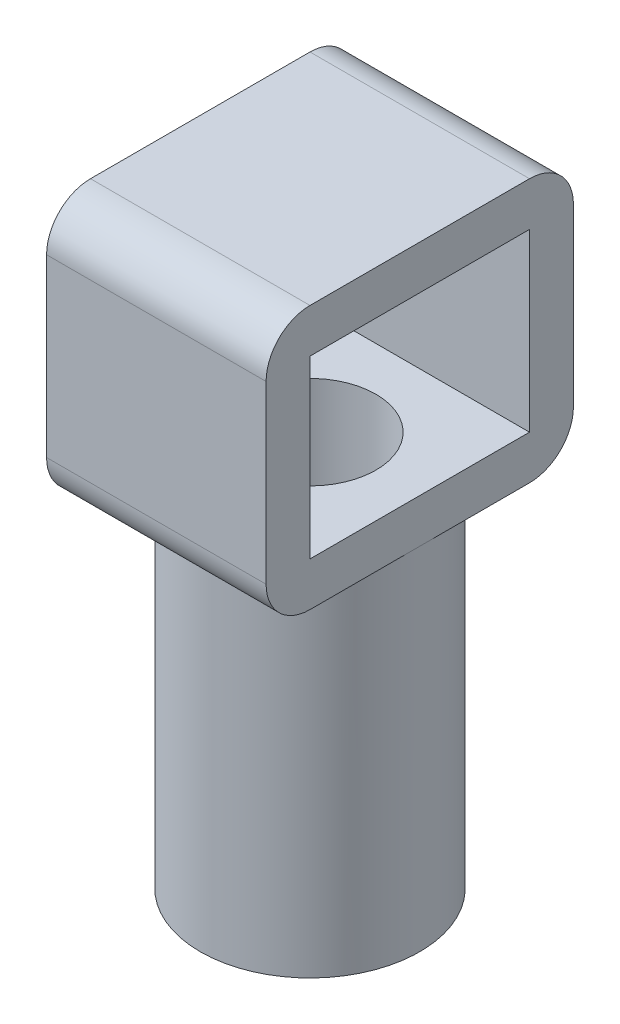
SolidWorks part; units mm, degrees
ref_plane "Front Plane" through (0, 0, 0) normal (0, 0, 1) x (1, 0, 0)
ref_plane "Top Plane" through (0, 0, 0) normal (0, 1, 0) x (1, 0, 0)
ref_plane "Right Plane" through (0, 0, 0) normal (1, 0, 0) x (0, 0, -1)
sketch "Sketch1" plane through (0, 0, 0) normal (0, 1, 0) x (1, 0, 0)
  circle A0 centre (0, 0) radius 12.5
  dimension "D1" = 25
extrude "Boss-Extrude1" add sketch "Sketch1" along normal blind 40
sketch "Sketch2" plane through (0, 40, 0) normal (0, 1, 0) x (1, 0, 0)
  line L1 (12.5, -17.5) -> (-12.5, -17.5)
  line L2 (12.5, -17.5) -> (12.5, 17.5)
  line L3 (12.5, 17.5) -> (-12.5, 17.5)
  line L4 (-12.5, -17.5) -> (-12.5, 17.5)
  line L5 (12.5, -17.5) -> (-12.5, 17.5) construction
  line L6 (12.5, 17.5) -> (-12.5, -17.5) construction
  point P0 (0, 0)
  dimension "D1" = 25
  dimension "D2" = 35
extrude "Boss-Extrude2" add sketch "Sketch2" along normal blind 30
sketch "Sketch3" plane through (12.5, 0, 0) normal (1, 0, 0) x (0, 0, -1)
  line L0 (-17.5, 70) -> (17.5, 70) construction
  line L1 (-12.5, 45) -> (12.5, 45)
  line L2 (-12.5, 45) -> (-12.5, 65)
  line L3 (-12.5, 65) -> (12.5, 65)
  line L4 (12.5, 45) -> (12.5, 65)
  line L5 (-12.5, 45) -> (12.5, 65) construction
  line L6 (-12.5, 65) -> (12.5, 45) construction
  line L7 (-12.5, 40) -> (0, 40) construction
  line L8 (17.5, 70) -> (17.5, 40) construction
  line L9 (-17.5, 70) -> (-17.5, 40) construction
  point P0 (0, 55)
  point P13 (-17.5, 55)
  dimension "D1" = 5
  dimension "D2" = 5
  dimension "D3" = 5
  dimension "D4" = 5
extrude "Cut-Extrude1" cut sketch "Sketch3" against normal through all
fillet "Fillet1" radius 5 4 edges at (0, 40, -17.5) (0, 70, -17.5) (0, 70, 17.5) (0, 40, 17.5)
sketch "Sketch4" plane through (0, 0, 0) normal (0, -1, 0) x (1, 0, 0)
  circle A0 centre (0, 0) radius 7.5
  dimension "D1" = 15
extrude "Cut-Extrude2" cut sketch "Sketch4" against normal blind 65
